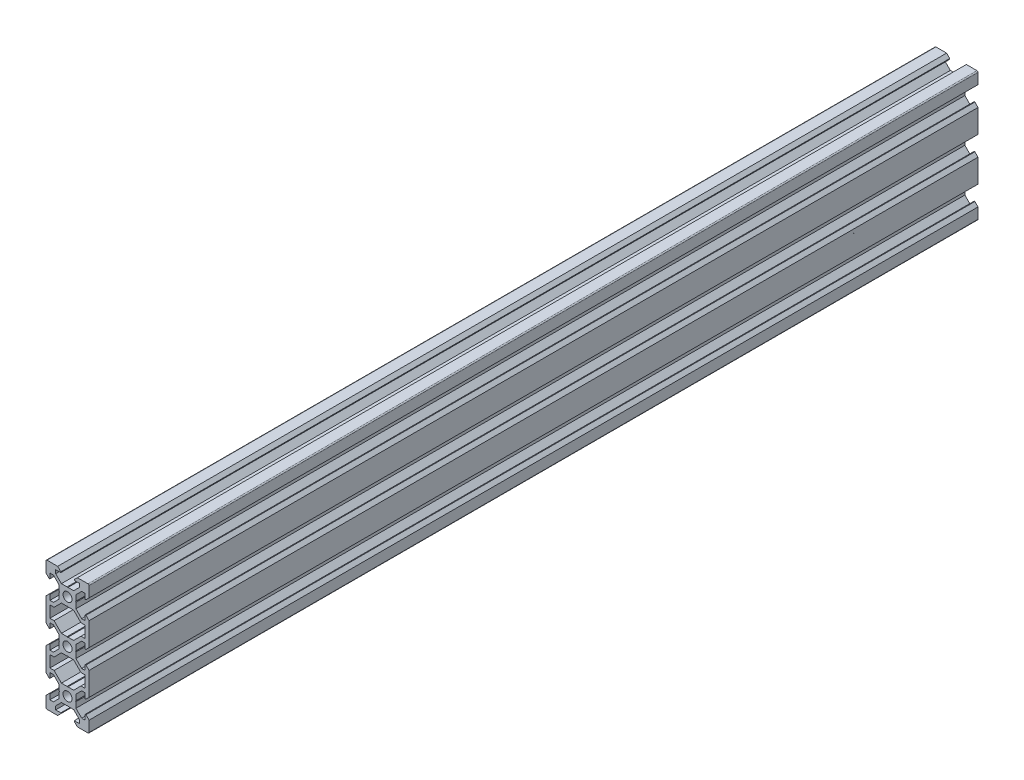
SolidWorks part; units mm, degrees
ref_plane "Plan de face" through (0, 0, 0) normal (0, 0, 1) x (1, 0, 0)
ref_plane "Plan de dessus" through (0, 0, 0) normal (0, 1, 0) x (1, 0, 0)
ref_plane "Plan de droite" through (0, 0, 0) normal (1, 0, 0) x (0, 0, -1)
ref_axis "Axe" through (0, 0, -13.782) along (0, 0, 1)
sketch "Esquisse1" plane through (0, 0, 0) normal (0, 0, 1) x (1, 0, 0)
  line L0 (0, 27.6392) -> (0, -27.6392) construction
  line L1 (-33.6074, 0) -> (33.6074, 0) construction
  line L2 (0, 0) -> (-22.2114, 22.2114) construction
  line L3 (-9.5, 10) -> (-4.58, 10)
  line L4 (-4.58, 10) -> (-3.125, 8.545)
  line L5 (-3.125, 8.545) -> (-3.125, 8.2)
  line L6 (-3.125, 8.2) -> (-5.5, 8.2)
  line L7 (-2.8393, 3.9) -> (-5.5, 6.5607)
  line L8 (-2.8393, 3.9) -> (-0.21, 3.9)
  line L9 (-5.5, 6.5607) -> (-5.5, 8.2)
  line L10 (0, 3.69) -> (0, 2.1)
  line L11 (-3.9, 2.8393) -> (-6.5607, 5.5)
  line L12 (-8.545, 3.125) -> (-8.2, 3.125)
  line L13 (-8.2, 3.125) -> (-8.2, 5.5)
  line L14 (-6.5607, 5.5) -> (-8.2, 5.5)
  line L15 (-10, 4.58) -> (-8.545, 3.125)
  line L16 (-10, 9.5) -> (-10, 4.58)
  line L17 (-0.21, 3.9) -> (0, 3.69)
  line L18 (-3.9, 2.8393) -> (-3.9, 0.21)
  line L19 (-6.2393, -12.7) -> (-8.2, -12.7)
  line L20 (-3.9, 0.21) -> (-3.69, 0)
  line L21 (-0.21, -3.9) -> (0, -3.69)
  line L22 (0, -3.69) -> (0, -2.1)
  line L23 (-6.5607, -5.5) -> (-8.2, -5.5)
  line L24 (-2.8393, -3.9) -> (-0.21, -3.9)
  line L25 (-8.545, -3.125) -> (-8.2, -3.125)
  line L26 (-10, -4.58) -> (-8.545, -3.125)
  line L27 (-8.2, -3.125) -> (-8.2, -5.5)
  line L28 (-2.8393, -3.9) -> (-6.2393, -7.3)
  line L29 (-3.9, -2.8393) -> (-6.5607, -5.5)
  line L30 (-3.9, -2.8393) -> (-3.9, -0.21)
  line L31 (-3.9, -0.21) -> (-3.69, 0)
  line L32 (-6.2393, -7.3) -> (-8.2, -7.3)
  line L33 (-8.2, -7.3) -> (-8.2, -12.7)
  line L34 (-8.2, -10) -> (-10, -10) construction
  line L35 (-10, -15.42) -> (-10, -4.58)
  line L36 (-3.9, -19.79) -> (-3.69, -20)
  line L37 (-3.9, -17.1607) -> (-3.9, -19.79)
  line L38 (-3.9, -17.1607) -> (-6.5607, -14.5)
  line L39 (-2.8393, -16.1) -> (-6.2393, -12.7)
  line L40 (-8.2, -16.875) -> (-8.2, -14.5)
  line L41 (-10, -15.42) -> (-8.545, -16.875)
  line L42 (-8.545, -16.875) -> (-8.2, -16.875)
  line L43 (-2.8393, -16.1) -> (-0.21, -16.1)
  line L44 (-6.5607, -14.5) -> (-8.2, -14.5)
  line L45 (0, -16.31) -> (0, -17.9)
  line L46 (-0.21, -16.1) -> (0, -16.31)
  line L47 (-8.2, -30) -> (-10, -30) construction
  line L48 (-3.69, -20) -> (0, -20) construction
  line L49 (-0.21, -23.9) -> (0, -23.69)
  line L50 (0, -23.69) -> (0, -22.1)
  line L51 (-6.5607, -25.5) -> (-8.2, -25.5)
  line L52 (-2.8393, -23.9) -> (-0.21, -23.9)
  line L53 (-8.545, -23.125) -> (-8.2, -23.125)
  line L54 (-10, -24.58) -> (-8.545, -23.125)
  line L55 (-8.2, -23.125) -> (-8.2, -25.5)
  line L56 (-2.8393, -23.9) -> (-6.2393, -27.3)
  line L57 (-3.9, -22.8393) -> (-6.5607, -25.5)
  line L58 (-3.9, -22.8393) -> (-3.9, -20.21)
  line L59 (-3.9, -20.21) -> (-3.69, -20)
  line L60 (-10, -24.58) -> (-10, -35.42)
  line L61 (-8.2, -32.7) -> (-8.2, -27.3)
  line L62 (-6.2393, -32.7) -> (-8.2, -32.7)
  line L63 (-3.9, -39.79) -> (-3.69, -40)
  line L64 (-3.9, -37.1607) -> (-3.9, -39.79)
  line L65 (-3.9, -37.1607) -> (-6.5607, -34.5)
  line L66 (-2.8393, -36.1) -> (-6.2393, -32.7)
  line L67 (-8.2, -36.875) -> (-8.2, -34.5)
  line L68 (-10, -35.42) -> (-8.545, -36.875)
  line L69 (-8.545, -36.875) -> (-8.2, -36.875)
  line L70 (-2.8393, -36.1) -> (-0.21, -36.1)
  line L71 (-6.5607, -34.5) -> (-8.2, -34.5)
  line L72 (0, -36.31) -> (0, -37.9)
  line L73 (-0.21, -36.1) -> (0, -36.31)
  line L74 (-3.9, -40.21) -> (-3.69, -40)
  line L75 (-6.2393, -27.3) -> (-8.2, -27.3)
  line L76 (-3.9, -42.8393) -> (-3.9, -40.21)
  line L77 (-0.21, -43.9) -> (0, -43.69)
  line L78 (-10, -49.5) -> (-10, -44.58)
  line L79 (-10, -44.58) -> (-8.545, -43.125)
  line L80 (-6.5607, -45.5) -> (-8.2, -45.5)
  line L81 (-8.2, -43.125) -> (-8.2, -45.5)
  line L82 (-8.545, -43.125) -> (-8.2, -43.125)
  line L83 (-3.9, -42.8393) -> (-6.5607, -45.5)
  line L84 (0, -43.69) -> (0, -42.1)
  line L85 (-5.5, -46.5607) -> (-5.5, -48.2)
  line L86 (-2.8393, -43.9) -> (-0.21, -43.9)
  line L87 (-2.8393, -43.9) -> (-5.5, -46.5607)
  line L88 (-3.125, -48.2) -> (-5.5, -48.2)
  line L89 (-3.125, -48.545) -> (-3.125, -48.2)
  line L90 (-4.58, -50) -> (-3.125, -48.545)
  line L91 (-9.5, -50) -> (-4.58, -50)
  arc A0 (0, -2.1) -> (0, 2.1) centre (0, 0) cw
  arc A1 (-9.5, 10) -> (-10, 9.5) centre (-9.5, 9.5) ccw
  arc A2 (0, -37.9) -> (0, -42.1) centre (0, -40) ccw
  arc A3 (-9.5, -50) -> (-10, -49.5) centre (-9.5, -49.5) cw
  arc A4 (0, -17.9) -> (0, -22.1) centre (0, -20) ccw
  point P4 (0, 0)
  point P7 (0, 0)
  point P30 (-10, 10)
  point P60 (0, -20)
  point P111 (-10, -50)
  dimension "D5" = 11
  dimension "D2" = 2.1
  dimension "D3" = 6.25
  dimension "D10" = 0.5
  dimension "D4" = 9.16
  dimension "D6" = 1.5
  dimension "D7" = 1.8
  dimension "D8" = 4.3
  dimension "D9" = 20
  dimension "D11" = 0.42
  dimension "D12" = 10
  dimension "D13" = 1.8
extrude "Boss.-Extru.1" add sketch "Esquisse1" along normal blind 412.76
sketch "Esquisse3" plane through (0, 0, 412.76) normal (0, 0, 1) x (1, 0, 0)
  line L0 (0, 0) -> (-9.8536, 9.8536) construction
  line L1 (-8.2, 8.2) -> (-8.2, 6.57)
  line L2 (-8.2, 6.57) -> (-7.54, 6.57)
  line L3 (-7.54, 6.57) -> (-6.57, 7.54)
  line L4 (-8.2, 3.125) -> (-8.2, 5.5) construction
  line L5 (-6.57, 8.2) -> (-6.57, 7.54)
  line L6 (-8.2, 8.2) -> (-6.57, 8.2)
  line L7 (-5.5, 6.5607) -> (-5.5, 8.2) construction
  line L8 (-3.69, -20) -> (0, -20) construction
  line L9 (-8.2, -48.2) -> (-6.57, -48.2)
  line L10 (-6.57, -48.2) -> (-6.57, -47.54)
  line L11 (-7.54, -46.57) -> (-6.57, -47.54)
  line L12 (-8.2, -46.57) -> (-7.54, -46.57)
  line L13 (-8.2, -48.2) -> (-8.2, -46.57)
  arc A0 (-9.5, 10) -> (-10, 9.5) centre (-9.5, 9.5) ccw construction
  point P13 (-7.055, 7.055)
  point P14 (-6.57, 7.87)
  point P26 (-7.055, -47.055)
  dimension "D1" = 1.07
extrude "Enlèv. mat.-Extru.1" [suppressed] cut sketch "Esquisse3" against normal through all
mirror "Symétrie1" about plane through (0, 3.69, 412.76) normal (-1, 0, 0) of "Enlèv. mat.-Extru.1", "Boss.-Extru.1"
